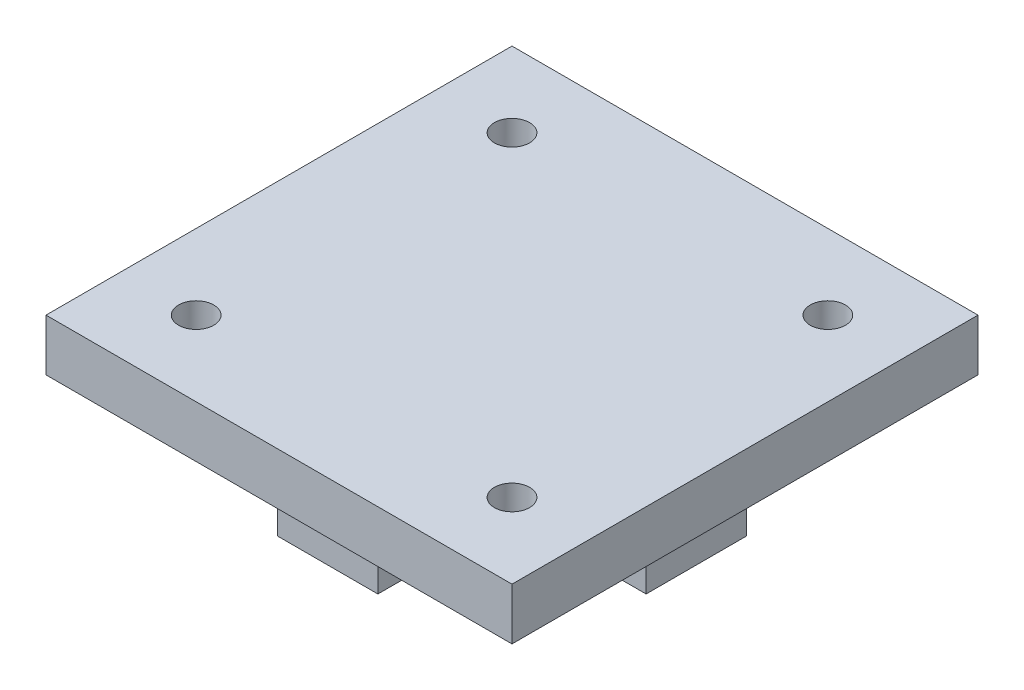
SolidWorks part; units mm, degrees
ref_plane "Front Plane" through (0, 0, 0) normal (0, 0, 1) x (1, 0, 0)
ref_plane "Top Plane" through (0, 0, 0) normal (0, 1, 0) x (1, 0, 0)
ref_plane "Right Plane" through (0, 0, 0) normal (1, 0, 0) x (0, 0, -1)
sketch "Sketch1" plane through (0, 0, 0) normal (0, 1, 0) x (1, 0, 0)
  line L1 (-22.5, 22.5) -> (22.5, 22.5)
  line L2 (-22.5, 22.5) -> (-22.5, -22.5)
  line L3 (-22.5, -22.5) -> (22.5, -22.5)
  line L4 (22.5, 22.5) -> (22.5, -22.5)
  line L5 (-22.5, 22.5) -> (22.5, -22.5) construction
  line L6 (-22.5, -22.5) -> (22.5, 22.5) construction
  point P0 (0, 0)
  dimension "D1" = 45
  dimension "D2" = 45
extrude "Boss-Extrude1" add sketch "Sketch1" against normal blind 5
sketch "Sketch2" plane through (0, -5, 0) normal (0, -1, 0) x (1, 0, 0)
  line L0 (-4.85, 12) -> (-4.85, 17.8)
  line L1 (-12, -4.85) -> (-17.8, -4.85)
  line L2 (-12, -4.85) -> (-12, 4.85)
  line L3 (-12, 4.85) -> (-17.8, 4.85)
  line L4 (-17.8, -4.85) -> (-17.8, 4.85)
  line L5 (-12, -4.85) -> (-17.8, 4.85) construction
  line L6 (-12, 4.85) -> (-17.8, -4.85) construction
  line L7 (-4.85, 12) -> (4.85, 12)
  line L8 (4.85, 12) -> (4.85, 17.8)
  line L9 (-4.85, 17.8) -> (4.85, 17.8)
  line L10 (-4.85, 12) -> (4.85, 17.8) construction
  line L11 (4.85, 12) -> (-4.85, 17.8) construction
  line L12 (12, 4.85) -> (17.8, 4.85)
  line L13 (12, 4.85) -> (12, -4.85)
  line L14 (12, -4.85) -> (17.8, -4.85)
  line L15 (17.8, 4.85) -> (17.8, -4.85)
  line L16 (12, 4.85) -> (17.8, -4.85) construction
  line L17 (12, -4.85) -> (17.8, 4.85) construction
  line L18 (4.85, -12) -> (4.85, -17.8)
  line L19 (4.85, -12) -> (-4.85, -12)
  line L20 (-4.85, -12) -> (-4.85, -17.8)
  line L21 (4.85, -17.8) -> (-4.85, -17.8)
  line L22 (4.85, -12) -> (-4.85, -17.8) construction
  line L23 (-4.85, -12) -> (4.85, -17.8) construction
  point P0 (-14.9, 0)
  point P5 (0, 14.9)
  point P6 (0, 0)
  point P13 (14.9, 0)
  point P18 (0, -14.9)
  point P23 (0, 0)
  dimension "D1" = 5.8
  dimension "D2" = 9.7
  dimension "D3" = 12
  dimension "D4" = 4
extrude "Boss-Extrude2" add sketch "Sketch2" along normal blind 7
sketch "Sketch3" plane through (0, 0, 0) normal (0, 1, 0) x (1, 0, 0)
  line L1 (-15.25, 15.25) -> (15.25, 15.25) construction
  line L2 (-15.25, 15.25) -> (-15.25, -15.25) construction
  line L3 (-15.25, -15.25) -> (15.25, -15.25) construction
  line L4 (15.25, 15.25) -> (15.25, -15.25) construction
  line L5 (-15.25, 15.25) -> (15.25, -15.25) construction
  line L6 (-15.25, -15.25) -> (15.25, 15.25) construction
  circle A0 centre (-15.25, 15.25) radius 1.7
  circle A1 centre (15.25, 15.25) radius 1.7
  circle A2 centre (-15.25, -15.25) radius 1.7
  circle A3 centre (15.25, -15.25) radius 1.7
  point P0 (0, 0)
  dimension "D3" = 3.4
  dimension "D1" = 30.5
  dimension "D2" = 30.5
extrude "Cut-Extrude1" cut sketch "Sketch3" against normal through all both and the other way through all
sketch "Sketch4" plane through (0, -5, 0) normal (0, -1, 0) x (1, 0, 0)
  line L0 (12.6, 13.72) -> (15.25, 12.19)
  line L1 (-13.72, 12.6) -> (-12.19, 15.25)
  line L2 (-12.19, 15.25) -> (-13.72, 17.9)
  line L3 (-13.72, 17.9) -> (-16.78, 17.9)
  line L4 (-16.78, 17.9) -> (-18.31, 15.25)
  line L5 (-18.31, 15.25) -> (-16.78, 12.6)
  line L6 (-16.78, 12.6) -> (-13.72, 12.6)
  line L7 (15.25, 12.19) -> (17.9, 13.72)
  line L8 (17.9, 13.72) -> (17.9, 16.78)
  line L9 (17.9, 16.78) -> (15.25, 18.31)
  line L10 (15.25, 18.31) -> (12.6, 16.78)
  line L11 (12.6, 16.78) -> (12.6, 13.72)
  line L12 (13.72, -12.6) -> (12.19, -15.25)
  line L13 (12.19, -15.25) -> (13.72, -17.9)
  line L14 (13.72, -17.9) -> (16.78, -17.9)
  line L15 (16.78, -17.9) -> (18.31, -15.25)
  line L16 (18.31, -15.25) -> (16.78, -12.6)
  line L17 (16.78, -12.6) -> (13.72, -12.6)
  line L18 (-12.6, -13.72) -> (-15.25, -12.19)
  line L19 (-15.25, -12.19) -> (-17.9, -13.72)
  line L20 (-17.9, -13.72) -> (-17.9, -16.78)
  line L21 (-17.9, -16.78) -> (-15.25, -18.31)
  line L22 (-15.25, -18.31) -> (-12.6, -16.78)
  line L23 (-12.6, -16.78) -> (-12.6, -13.72)
  circle A0 centre (-15.25, 15.25) radius 2.65 construction
  point P1 (0, 0)
  point P30 (0, 0)
  dimension "D1" = 5.3
  dimension "D2" = 4
extrude "Cut-Extrude2" cut sketch "Sketch4" against normal blind 2.5
